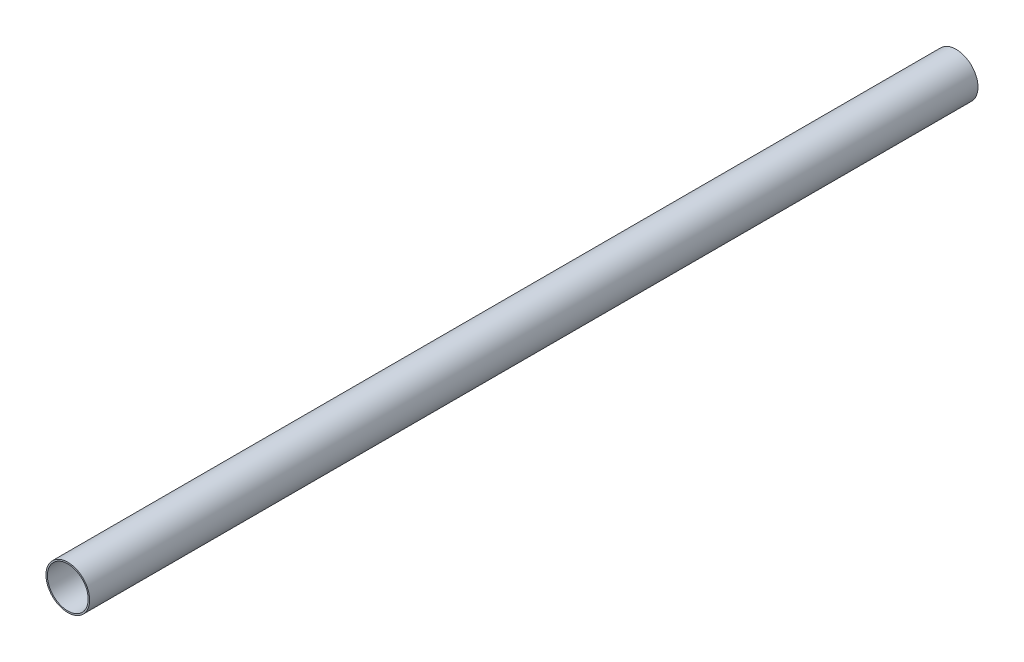
SolidWorks part; units mm, degrees
material "CarbonFiber"
ref_plane "Front Plane" through (0, 0, 0) normal (0, 0, 1) x (1, 0, 0)
ref_plane "Top Plane" through (0, 0, 0) normal (0, 1, 0) x (1, 0, 0)
ref_plane "Right Plane" through (0, 0, 0) normal (1, 0, 0) x (0, 0, -1)
sketch "Эскиз1" plane through (0, 0, 0) normal (0, 0, 1) x (1, 0, 0)
  circle A0 centre (0, 0) radius 15
  circle A1 centre (0, 0) radius 14
  dimension "D1" = 30
  dimension "D2" = 1
extrude "Бобышка-Вытянуть1" add sketch "Эскиз1" along normal mid plane 610
equation "\"DTailTube\"= 16mm'Диаметр трубки хвостового оперения"
equation "\"FusLenght\"= 700mm"
equation "\"DMotor\"= 35.2mm"
equation "\"MotorArm\"= 320mm"
equation "\"DFus\"= 150mm"
equation "\"DFusTube\"= 30mm'Диаметр трубки внутри фюзеляжа"
equation "\"FusTubeHeight\"= 40mm"
equation "\"FusCentralPartLenght\"= 410mm"
equation "\"FusNoseLenght\"= 150mm"
equation "\"WingOffset\"= 1mm'Расстояние от внутренней поверхности фюзеляжа до профиля крыла по вертикали"
equation "\"EllipseRatio\"= 0.95'Центральная часть фюзеляжа - эллипс. Этот параметр - отношение длин осей эллипса"
equation "\"FrameOffset\"= 0.6mm"
equation "\"DThreadedInsert\"= 3mm'Внешний диамер резьбовых втулок"
equation "\"CenterSectionLenght\"= 140mm'Длина центроплана"
equation "\"b\"= 1700mm'Размах"
equation "\"cwr\"= 236mm'Корневая хорда крыла"
equation "\"TR\"= 0.75'Сужение крыла"
equation "\"cwt\"= \"TR\" * \"cwr\"'Концевая хорда крыла"
equation "\"DWingMainSpar\"= 16mm'Диаметр главного лонжерона крыла"
equation "\"DWingSecondSpar\"= 8mm'Диаметр второго лонжерона крыла"
equation "\"WingSparsDistance\"= 80mm'Расстояния между отверстиями по лонжерон крыла"
equation "\"c\"= 210mm'САХ крыла"
equation "\"D1@Эскиз1\"=\"DFusTube\""
equation "\"D1@Бобышка-Вытянуть1\"=\"FusTubeLenght\""
equation "\"FusTubeLenght\"= \"FusLenght\"-90mm'Длина трубки фюзеляжа"
equation "\"bt\"=291mm'Высота лопатки хвоста"
equation "\"ct\"=182mm'Корневая хорда хвоста"
equation "\"lambda_t\"=0.3'Доля хвоста, занатая рулем высоты"
equation "\"TailTubeLenght\"=680mm'Длина хвостовой балки"
equation "\"DStringer\"=6mm'Диаметр стрингеров"
equation "\"TailConnectorBaseLenght\"=20mm'Высота основания конектора хвоста"
equation "\"CargoHolderHoleDistance\"=30mm'Расстояние между крепежными отверстиями для держателя груза"
equation "\"FuselageThickness\"=1.2mm'Толщина фюзеляжа"
equation "\"DTailSpar\"=6mm'Диаметр лонжерона хвостового оперения"
equation "\"TailSparDistance\"=40mm'Расстояние между лонжеронами хвостового оперения"
equation "\"ThreadedInsertLenght\"=4mm'Длина резьбовых втулок"
equation "\"ThreadedInsertThread\"=2mm'Диаметр резьбы втулки"
equation "\"CrossSectionWidth\"=15mm'Ширина кольцевой части шпангоута"
equation "\"HingeLenght\"=30mm'Длина отверстия под шарнир хвостового оперения"
equation "\"HingeWidth\"=2.4mm'Высота отверстия под шарнир ХО"
equation "\"HingeDepth\"=15mm'Глубина отверстия под шарнир ХО"
equation "\"DMagnet\"=3mm'Диаметр магнитов"
equation "\"MagnetHeight\"=2mm'Высота магнитов"
equation "\"PlywoodThickness\"=2.9mm'Толщина фанеры"
